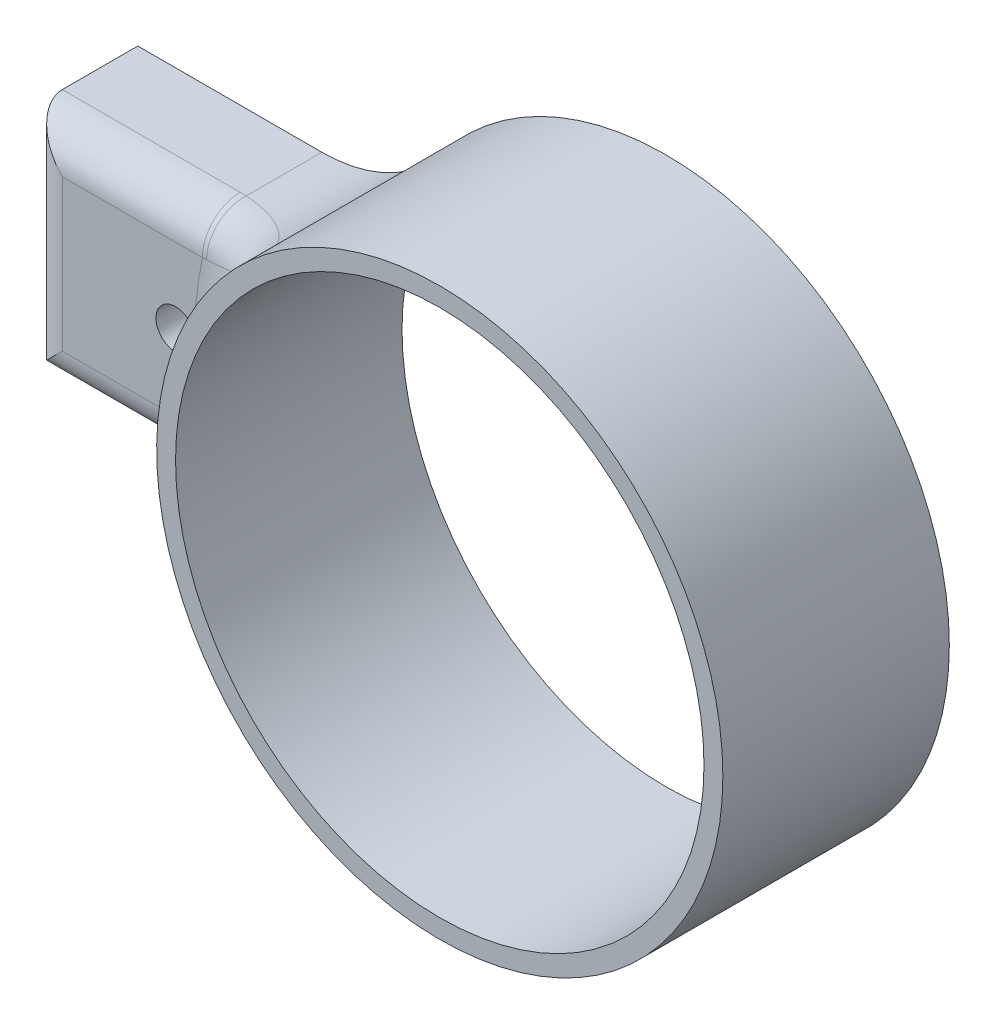
SolidWorks part; units mm, degrees
ref_plane "Plan de face" through (0, 0, 0) normal (0, 0, 1) x (1, 0, 0)
ref_plane "Plan de dessus" through (0, 0, 0) normal (0, 1, 0) x (1, 0, 0)
ref_plane "Plan de droite" through (0, 0, 0) normal (1, 0, 0) x (0, 0, -1)
sketch "Esquisse5" plane through (0, 0, 0) normal (0, 0, 1) x (1, 0, 0)
  line L0 (-1000, 0) -> (49000, 0) construction
  line L1 (-45.6207, 15) -> (-70, 15)
  line L2 (-70, 15) -> (-70, -15)
  line L3 (-45.6207, -15) -> (-70, -15)
  circle A0 centre (0, 0) radius 35
  arc A1 (-29.7526, -22.8261) -> (-29.7526, 22.8261) centre (0, 0) ccw
  arc A2 (-45.6207, 15) -> (-29.7526, 22.8261) centre (-45.6207, 35) ccw
  arc A3 (-45.6207, -15) -> (-29.7526, -22.8261) centre (-45.6207, -35) cw
  point P14 (-70, 0)
  dimension "D1" = 70
  dimension "D2" = 75
  dimension "D5" = 20
  dimension "D3" = 15
  dimension "D4" = 70
extrude "Boss.-Extru.4" add sketch "Esquisse5" along normal blind 15
sketch "Esquisse8" plane through (0, 0, 15) normal (0, 0, 1) x (1, 0, 0)
  circle A0 centre (0, 0) radius 35
  circle A1 centre (0, 0) radius 37.5
  circle A2 centre (0, 0) radius 35 construction
  arc A3 (-29.7526, -22.8261) -> (-29.7526, 22.8261) centre (0, 0) ccw construction
extrude "Boss.-Extru.7" add sketch "Esquisse8" along normal blind 15
fillet "Congé3" radius 10 1 edges at (-37.5, 0, 15)
fillet "Congé4" radius 5 7 edges at (-45.3438, 15.0019, 15) (-45.3438, -15.0019, 15) (-36.9031, 16.9999, 17.733) (-57.8104, 15, 15) (-70, 0, 15) (-57.8104, -15, 15) (-36.9031, -16.9999, 17.733)
sketch "Esquisse12" plane through (-70, 0, 0) normal (-1, 0, 0) x (0, 0, 1)
  line L5 (0, 10) -> (10, 10) construction
  line L8 (0, 15) -> (0, -15) construction
  line L9 (10, 10) -> (10, -10) construction
  line L10 (-1000, 0) -> (49000, 0) construction
  line L11 (0, -10) -> (10, -10) construction
  line L12 (10, 15) -> (0, 15) construction
  line L14 (0, 10) -> (0, -10) construction
  line L15 (-0.2, 10.2) -> (10.2, 10.2)
  line L16 (10.2, 10.2) -> (10.2, -10.2)
  line L17 (-0.2, -10.2) -> (10.2, -10.2)
  line L18 (-0.2, 10.2) -> (-0.2, -10.2)
  line L20 (15, -10) -> (15, 10) construction
  point P9 (10, 0)
  dimension "D1" = 5
  dimension "D2" = 5
  dimension "D3" = 0.2
extrude "Enlèv. mat.-Extru.2" cut sketch "Esquisse12" against normal blind 30
sketch "Esquisse13" plane through (0, 0, 15) normal (0, 0, 1) x (1, 0, 0)
  line L0 (-69.996, -10.2) -> (-69.996, 10.2) construction
  circle A0 centre (-49.996, 0) radius 2.6
  dimension "D1" = 5.2
  dimension "D2" = 20
extrude "Enlèv. mat.-Extru.3" cut sketch "Esquisse13" against normal up to next and the other way through all
